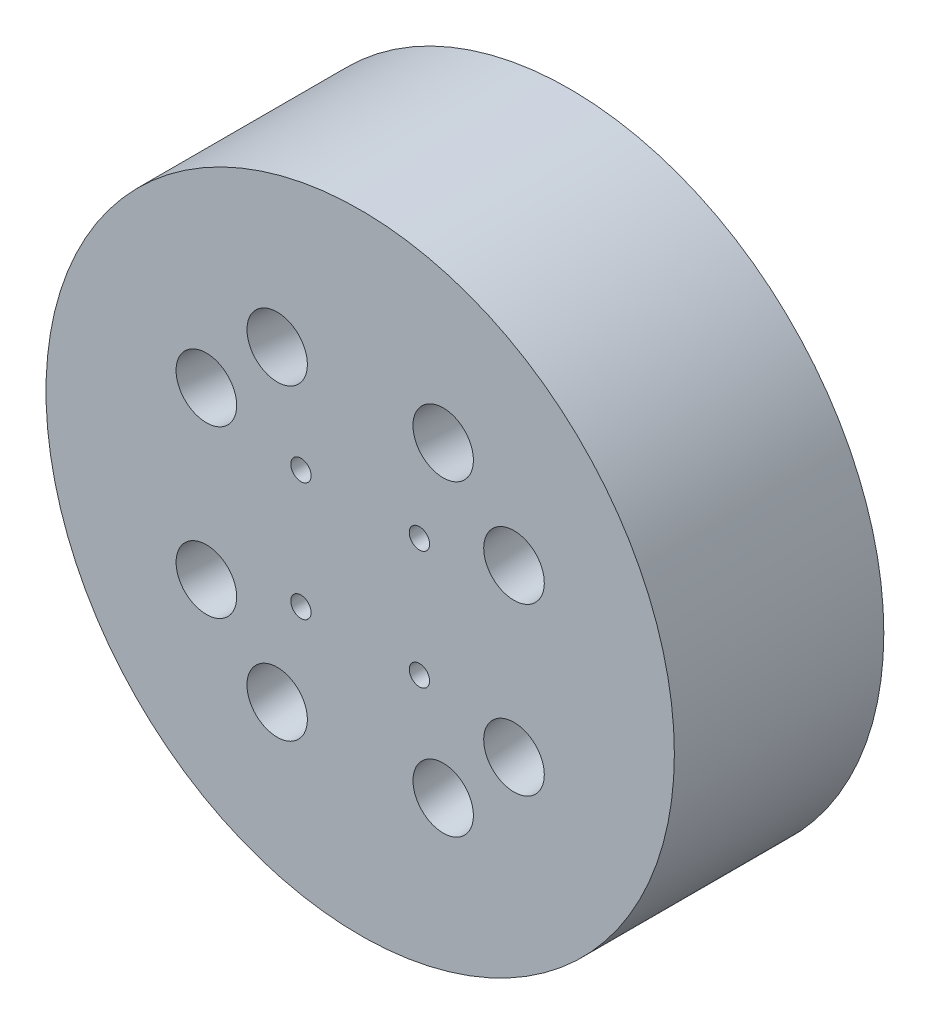
SolidWorks part; units mm, degrees
ref_plane "Front Plane" through (0, 0, 0) normal (0, 0, 1) x (1, 0, 0)
ref_plane "Top Plane" through (0, 0, 0) normal (0, 1, 0) x (1, 0, 0)
ref_plane "Right Plane" through (0, 0, 0) normal (1, 0, 0) x (0, 0, -1)
sketch "Sketch1" plane through (0, 0, 0) normal (0, 0, 1) x (1, 0, 0)
  circle A0 centre (0, 0) radius 15
  dimension "D1" = 30
extrude "Boss-Extrude1" add sketch "Sketch1" along normal blind 10
sketch "Sketch2" plane through (0, 0, 10) normal (0, 0, 1) x (1, 0, 0)
  line L0 (-15, 0) -> (15, 0) construction
  line L1 (0, 0) -> (10.6066, 10.6066) construction
  circle A0 centre (0, 0) radius 15 construction
  circle A1 centre (2.8284, 2.8284) radius 0.4849
  dimension "D2" = 0.9698
  dimension "D1" = 45
  dimension "D3" = 4
extrude "Cut-Extrude1" cut sketch "Sketch2" against normal blind 10
pattern_circular "CirPattern1" count 4 over 360 about axis through (0, 0, 10) along (0, 0, -1) of "Cut-Extrude1"
sketch "Sketch5" plane through (0, 0, 0) normal (0, 0, -1) x (-1, 0, 0)
  line L0 (0, 0) -> (15, 0) construction
  line L1 (0, 0) -> (12.9904, 7.5) construction
  line L2 (2.8284, 2.8284) -> (6.4952, 3.75) construction
  line L3 (2.8284, 2.8284) -> (1.7532, 7.1064) construction
  line L4 (0, 0) -> (10.6066, 10.6066) construction
  circle A0 centre (0, 0) radius 15 construction
  circle A1 centre (6.4952, 3.75) radius 1.3529
  dimension "D1" = 30
  dimension "D2" = 45
ref_plane "Plane1" through (-0.0253, 0.0064, 0.298) normal (0.0845, -0.0212, -0.9962) x (0.2438, 0.9698, 0)
sketch "Sketch7" plane through (-0.0253, 0.0064, 0.298) normal (0.0845, -0.0212, -0.9962) x (0.2438, 0.9698, 0)
  circle A0 centre (2.0537, -7.1859) radius 1.4413
  dimension "D1" = 2.8827
extrude "Cut-Extrude2" cut sketch "Sketch7" against normal through all both and the other way through all
ref_axis "Axis4" through (0, 0, -18.0578) along (0, 0, 1)
ref_plane "Plane2" through (0, 0, 0) normal (-0.7071, -0.7071, 0) x (0, 0, 1)
mirror "Mirror1" about plane through (0, 0, 0) normal (-0.7071, -0.7071, 0) of "Cut-Extrude2"
pattern_circular "CirPattern2" count 4 over 360 about axis through (0, 0, 10) along (0, 0, -1) of "Mirror1", "Cut-Extrude2"
